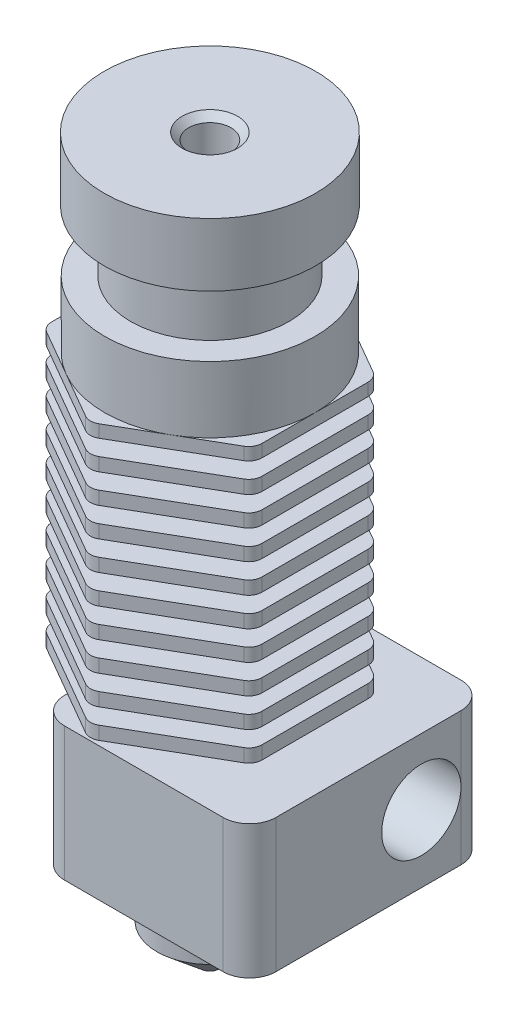
SolidWorks part; units mm, degrees
ref_plane "Front Plane" through (0, 0, 0) normal (0, 0, 1) x (1, 0, 0)
ref_plane "Top Plane" through (0, 0, 0) normal (0, 1, 0) x (1, 0, 0)
ref_plane "Right Plane" through (0, 0, 0) normal (1, 0, 0) x (0, 0, -1)
sketch "Sketch1" plane through (0, 0, 0) normal (0, 1, 0) x (1, 0, 0)
  line L1 (0, 9.19) -> (-7.9588, 4.595)
  line L2 (-7.9588, 4.595) -> (-7.9588, -4.595)
  line L3 (-7.9588, -4.595) -> (0, -9.19)
  line L4 (0, -9.19) -> (7.9588, -4.595)
  line L5 (7.9588, -4.595) -> (7.9588, 4.595)
  line L6 (7.9588, 4.595) -> (0, 9.19)
  circle A0 centre (0, 0) radius 9.19 construction
  dimension "D1" = 18.38
extrude "Boss-Extrude1" add sketch "Sketch1" against normal blind 25.75
sketch "Sketch9" plane through (0, 0, 0) normal (0, 1, 0) x (1, 0, 0)
  circle A0 centre (0, 0) radius 6
  dimension "D1" = 12
extrude "Boss-Extrude4" add sketch "Sketch9" along normal blind 4.64
sketch "Sketch10" plane through (0, 4.64, 0) normal (0, 1, 0) x (1, 0, 0)
  circle A0 centre (0, 0) radius 8
  dimension "D1" = 16
extrude "Boss-Extrude5" add sketch "Sketch10" along normal blind 4.76
sketch "Sketch2" plane through (0, 0, 0) normal (0, 1, 0) x (1, 0, 0)
  circle A0 centre (0, 0) radius 2
  dimension "D1" = 4
extrude "Boss-Extrude2" add sketch "Sketch2" against normal blind 30
sketch "Sketch4" plane through (0, -30, 0) normal (0, -1, 0) x (1, 0, 0)
  line L0 (0, 9.19) -> (0, -9.19) construction
  line L1 (-6, 5) -> (6, 5)
  line L2 (-8, 3) -> (-8, -11)
  line L3 (-6, -13) -> (6, -13)
  line L4 (8, 3) -> (8, -11)
  line L5 (0, 0) -> (7.9588, 0) construction
  line L6 (7.9588, 4.595) -> (7.9588, -4.595) construction
  arc A0 (-8, -11) -> (-6, -13) centre (-6, -11) ccw
  arc A1 (6, -13) -> (8, -11) centre (6, -11) ccw
  arc A2 (6, 5) -> (8, 3) centre (6, 3) cw
  arc A3 (-6, 5) -> (-8, 3) centre (-6, 3) ccw
  point P15 (-8, -13)
  point P20 (8, 5)
  point P23 (-8, 5)
  dimension "D4" = 2
  dimension "D1" = 16
  dimension "D2" = 18
  dimension "D3" = 5
extrude "Boss-Extrude3" add sketch "Sketch4" along normal blind 10.11
fillet "Fillet1" radius 1 6 edges at (7.9588, -12.875, -4.595) (7.9588, -12.875, 4.595) (0, -12.875, 9.19) (-7.9588, -12.875, 4.595) (0, -12.875, -9.19) (-7.9588, -12.875, -4.595)
ref_plane "Plane2" through (0, 0, 0) normal (1, 0, 0) x (0, 0, -1)
ref_axis "Axis1" through (0, -46.6152, 0) along (0, 1, 0)
ref_plane "Plane3" through (0, 0, 0) normal (0, 0, -1) x (-1, 0, 0)
sketch "Sketch5" plane through (0, -40.11, 0) normal (0, -1, 0) x (1, 0, 0)
  circle A0 centre (0, 0) radius 4
  dimension "D1" = 8
extrude "Nozzle" add sketch "Sketch5" along normal blind 5
chamfer "Chamfer1" distance 2.8 angle 50 1 edges at (0, -45.11, -4) first distance on face at (0, -45.11, -4)
sketch "Sketch6" plane through (0, -25.75, 0) normal (0, -1, 0) x (1, 0, 0)
  line L6 (0.5, -8.9013) -> (7.4588, -4.8837)
  line L7 (7.9588, -4.0176) -> (7.9588, 4.0176)
  line L8 (7.4588, 4.8837) -> (0.5, 8.9013)
  line L9 (-0.5, 8.9013) -> (-7.4588, 4.8837)
  line L10 (-7.9588, 4.0176) -> (-7.9588, -4.0176)
  line L11 (-7.4588, -4.8837) -> (-0.5, -8.9013)
  line L12 (0.5, -8.9013) -> (7.4588, -4.8837)
  line L13 (7.9588, -4.0176) -> (7.9588, 4.0176)
  line L14 (7.4588, 4.8837) -> (0.5, 8.9013)
  line L15 (-0.5, 8.9013) -> (-7.4588, 4.8837)
  line L16 (-7.9588, 4.0176) -> (-7.9588, -4.0176)
  line L17 (-7.4588, -4.8837) -> (-0.5, -8.9013)
  circle A0 centre (0, 0) radius 2.75
  arc A6 (7.4588, -4.8837) -> (7.9588, -4.0176) centre (6.9588, -4.0176) ccw
  arc A7 (7.9588, 4.0176) -> (7.4588, 4.8837) centre (6.9588, 4.0176) ccw
  arc A8 (0.5, 8.9013) -> (-0.5, 8.9013) centre (0, 8.0353) ccw
  arc A9 (-7.4588, 4.8837) -> (-7.9588, 4.0176) centre (-6.9588, 4.0176) ccw
  arc A10 (-7.9588, -4.0176) -> (-7.4588, -4.8837) centre (-6.9588, -4.0176) ccw
  arc A11 (-0.5, -8.9013) -> (0.5, -8.9013) centre (0, -8.0353) ccw
  arc A12 (7.4588, -4.8837) -> (7.9588, -4.0176) centre (6.9588, -4.0176) ccw
  arc A13 (7.9588, 4.0176) -> (7.4588, 4.8837) centre (6.9588, 4.0176) ccw
  arc A14 (0.5, 8.9013) -> (-0.5, 8.9013) centre (0, 8.0353) ccw
  arc A15 (-7.4588, 4.8837) -> (-7.9588, 4.0176) centre (-6.9588, 4.0176) ccw
  arc A16 (-7.9588, -4.0176) -> (-7.4588, -4.8837) centre (-6.9588, -4.0176) ccw
  arc A17 (-0.5, -8.9013) -> (0.5, -8.9013) centre (0, -8.0353) ccw
  dimension "D2" = 5.5
  dimension "D1" = 0
extrude "Cut-Extrude1" cut sketch "Sketch6" against normal blind 1.2 from offset 1 offset against normal yes
pattern_linear "LPattern1" count 9 spacing 2.2 along (0, 1, 0) of "Cut-Extrude1"
sketch "Sketch7" plane through (0, 0, 0) normal (0, 1, 0) x (1, 0, 0)
  line L6 (7.9588, -4.0176) -> (7.9588, 4.0176)
  line L7 (7.4588, 4.8837) -> (0.5, 8.9013)
  line L8 (-0.5, 8.9013) -> (-7.4588, 4.8837)
  line L9 (-7.9588, 4.0176) -> (-7.9588, -4.0176)
  line L10 (-7.4588, -4.8837) -> (-0.5, -8.9013)
  line L11 (0.5, -8.9013) -> (7.4588, -4.8837)
  line L12 (7.9588, -4.0176) -> (7.9588, 4.0176)
  line L13 (7.4588, 4.8837) -> (0.5, 8.9013)
  line L14 (-0.5, 8.9013) -> (-7.4588, 4.8837)
  line L15 (-7.9588, 4.0176) -> (-7.9588, -4.0176)
  line L16 (-7.4588, -4.8837) -> (-0.5, -8.9013)
  line L17 (0.5, -8.9013) -> (7.4588, -4.8837)
  circle A0 centre (0, 0) radius 7.9588
  arc A6 (7.9588, 4.0176) -> (7.4588, 4.8837) centre (6.9588, 4.0176) ccw
  arc A7 (0.5, 8.9013) -> (-0.5, 8.9013) centre (0, 8.0353) ccw
  arc A8 (-7.4588, 4.8837) -> (-7.9588, 4.0176) centre (-6.9588, 4.0176) ccw
  arc A9 (-7.9588, -4.0176) -> (-7.4588, -4.8837) centre (-6.9588, -4.0176) ccw
  arc A10 (-0.5, -8.9013) -> (0.5, -8.9013) centre (0, -8.0353) ccw
  arc A11 (7.4588, -4.8837) -> (7.9588, -4.0176) centre (6.9588, -4.0176) ccw
  arc A12 (7.9588, 4.0176) -> (7.4588, 4.8837) centre (6.9588, 4.0176) ccw
  arc A13 (0.5, 8.9013) -> (-0.5, 8.9013) centre (0, 8.0353) ccw
  arc A14 (-7.4588, 4.8837) -> (-7.9588, 4.0176) centre (-6.9588, 4.0176) ccw
  arc A15 (-7.9588, -4.0176) -> (-7.4588, -4.8837) centre (-6.9588, -4.0176) ccw
  arc A16 (-0.5, -8.9013) -> (0.5, -8.9013) centre (0, -8.0353) ccw
  arc A17 (7.4588, -4.8837) -> (7.9588, -4.0176) centre (6.9588, -4.0176) ccw
  line M13 (7.9588, -4.0176) -> (7.9588, 4.0176)
  arc M14 (7.9588, 4.0176) -> (7.4588, 4.8837) centre (6.9588, 4.0176) ccw
  line M15 (7.4588, 4.8837) -> (0.5, 8.9013)
  arc M16 (0.5, 8.9013) -> (-0.5, 8.9013) centre (0, 8.0353) ccw
  line M17 (-0.5, 8.9013) -> (-7.4588, 4.8837)
  arc M18 (-7.4588, 4.8837) -> (-7.9588, 4.0176) centre (-6.9588, 4.0176) ccw
  line M19 (-7.9588, 4.0176) -> (-7.9588, -4.0176)
  arc M20 (-7.9588, -4.0176) -> (-7.4588, -4.8837) centre (-6.9588, -4.0176) ccw
  line M21 (-7.4588, -4.8837) -> (-0.5, -8.9013)
  arc M22 (-0.5, -8.9013) -> (0.5, -8.9013) centre (0, -8.0353) ccw
  line M23 (0.5, -8.9013) -> (7.4588, -4.8837)
  arc M24 (7.4588, -4.8837) -> (7.9588, -4.0176) centre (6.9588, -4.0176) ccw
  dimension "D1" = 0
extrude "Cut-Extrude2" cut sketch "Sketch7" against normal blind 5 contours A0 L15 M20 M21 | A0 L14 M18 M19 | A0 L13 M16 M17 | A0 L12 M14 M15 | A0 L17 M24 M13 | A0 L16 M22 M23 region at (7.1121, 0, 4.1062) region at (7.1121, 0, -4.1062) region at (0, 0, -8.2124) region at (0, 0, 8.2124) region at (-7.1121, 0, -4.1062) region at (-7.1121, 0, 4.1062)
sketch "Sketch8" plane through (0, 0, 0) normal (0, 1, 0) x (1, 0, 0)
  circle A0 centre (0, 0) radius 1.6
  dimension "D1" = 3.2
extrude "Cut-Extrude3" cut sketch "Sketch8" against normal blind 43 and the other way up to surface (9.4 mm away) other way up to face at (0, 9.4, 8)
chamfer "Chamfer2" distance 0.5 angle 45 1 edges at (0, 9.4, 1.6)
sketch "Sketch11" plane through (-8, 0, 0) normal (-1, 0, 0) x (0, 0, 1)
  line L0 (3, -30) -> (-11, -30) construction
  line L1 (-13, -40.11) -> (-13, -30) construction
  circle A0 centre (-8, -35) radius 3
  point P4 (-13, -35.055)
  dimension "D1" = 6
  dimension "D2" = 5
  dimension "D3" = 5
extrude "Cut-Extrude4" cut sketch "Sketch11" against normal up to next
